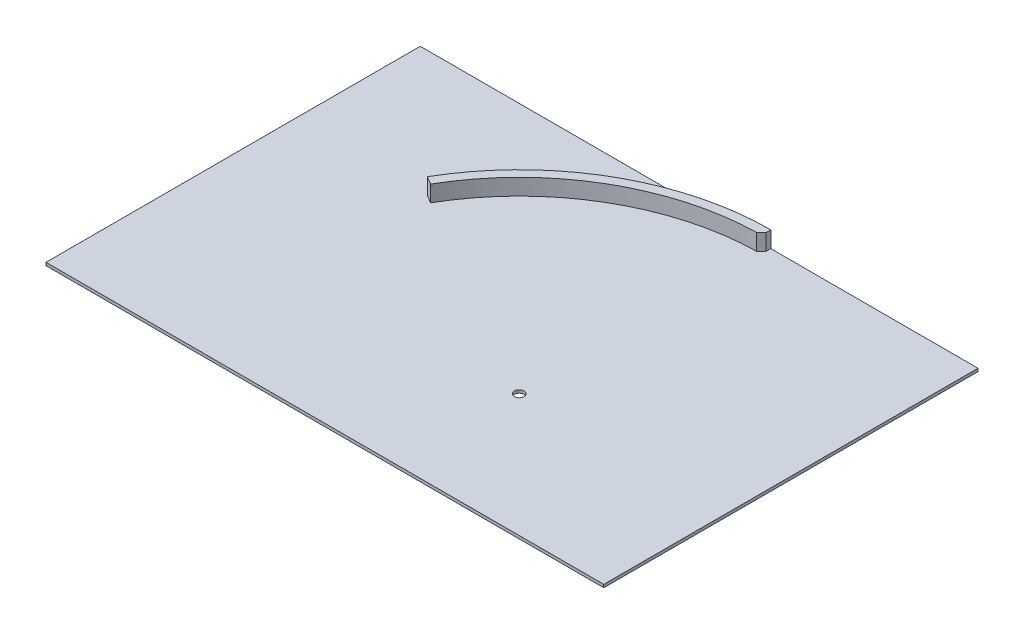
SolidWorks part; units mm, degrees
ref_plane "Front Plane" through (0, 0, 0) normal (0, 0, 1) x (1, 0, 0)
ref_plane "Top Plane" through (0, 0, 0) normal (0, 1, 0) x (1, 0, 0)
ref_plane "Right Plane" through (0, 0, 0) normal (1, 0, 0) x (0, 0, -1)
sketch "Sketch3" plane through (0, 0, 0) normal (0, 1, 0) x (1, 0, 0)
  line L1 (0, 0) -> (-839.8654, 0) construction
  line L2 (0, 0) -> (-451.1992, 260.5) construction
  line L3 (0, 541) -> (0, 521)
  line L4 (-468.5197, 270.5) -> (-451.1992, 260.5)
  circle A0 centre (0, 0) radius 250 construction
  arc A1 (0, 521) -> (-451.1992, 260.5) centre (0, 0) ccw
  arc A2 (0, 541) -> (-468.5197, 270.5) centre (0, 0) ccw
  dimension "D1" = 500
  dimension "D2" = 521
  dimension "D3" = 30
  dimension "D4" = 20
extrude "Boss-Extrude1" add sketch "Sketch3" along normal blind 35
sketch "Sketch4" plane through (0, 0, 0) normal (0, 1, 0) x (1, 0, 0)
  line L1 (-754.1392, -264.2) -> (445.8608, -264.2)
  line L2 (-754.1392, -264.2) -> (-754.1392, 541)
  line L3 (-754.1392, 541) -> (445.8608, 541)
  line L4 (445.8608, -264.2) -> (445.8608, 541)
  arc A0 (0, 541) -> (-468.5197, 270.5) centre (0, 0) ccw construction
  dimension "D1" = 1200
  dimension "D2" = 524.7
  dimension "D3" = 302.94
extrude "Boss-Extrude2" add sketch "Sketch4" against normal blind 6.35
chamfer "Chamfer1" distance 10 angle 45 1 edges at (0, 17.5, -521)
hole_wizard "Ø20.0mm Dowel Hole1" positions "Sketch6" profile "Sketch7" hole size "Ø20.0" standard "ANSI Metric" end condition through all
sketch "Sketch6" plane through (0, 0, 0) normal (0, 1, 0) x (1, 0, 0)
  point P0 (0, 0)
sketch "Sketch7" plane through (0, 0, 0) normal (1, 0, 0) x (0, 0, 1)
  line L0 (0, 0) -> (0, 6.35)
  line L1 (0, 6.35) -> (10.5, 6.35)
  line L2 (10.5, 6.35) -> (10.5, 0)
  line L5 (10.5, 0) -> (0, 0)
  line L11 (0, -6.35) -> (0, 107.95) construction
  dimension "Thru Hole Dia." = 21
  dimension "Thru Hole Depth" = 6.35
equation "\"D2@Sketch3\"=(\"D1@Sketch3\"/2)+271"
